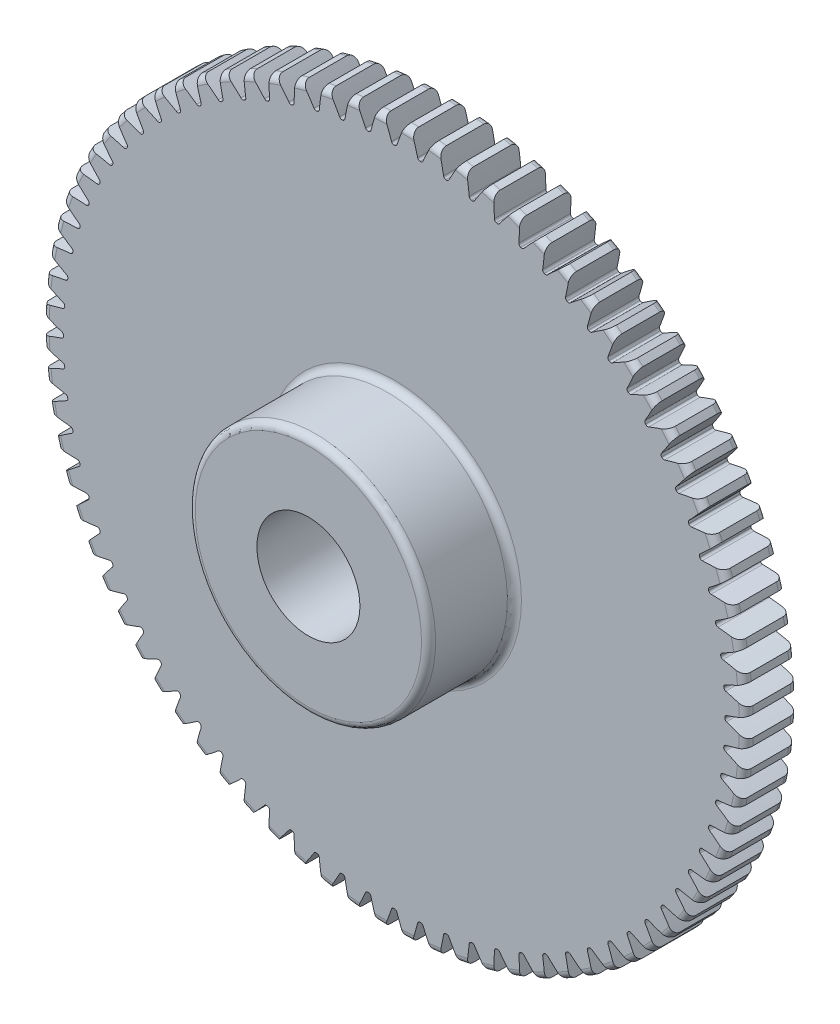
SolidWorks part; units mm, degrees
ref_plane "Front Plane" through (0, 0, 0) normal (0, 0, 1) x (1, 0, 0)
ref_plane "Top Plane" through (0, 0, 0) normal (0, 1, 0) x (1, 0, 0)
ref_plane "Right Plane" through (0, 0, 0) normal (1, 0, 0) x (0, 0, -1)
sketch "Sketch1" plane through (0, 0, 0) normal (0, 0, 1) x (1, 0, 0)
  line L0 (-1016, 0) -> (1016, 0) construction
  circle A0 centre (0, 0) radius 20.5 construction
  circle A1 centre (0, 0) radius 20 construction
  circle A2 centre (0, 0) radius 19.25 construction
  circle A3 centre (0, 0) radius 7 construction
  circle A4 centre (0, 0) radius 3 construction
  dimension "D2" = 0.5
  dimension "D3" = 1.25
  dimension "D1" = 1.25
sketch "Sketch2" plane through (0, 0, 0) normal (1, 0, 0) x (0, 0, -1)
  line L0 (0, 0) -> (-3, 0) construction
  line L1 (-3, 0) -> (-8, 0) construction
  dimension "Overall Width" = 8
  dimension "Face Width" = 3
sketch "Sketch4" plane through (0, 0, 0) normal (1, 0, 0) x (0, 0, -1)
  line L0 (-8, 3) -> (-8, 7)
  line L1 (-8, 7) -> (-3, 7)
  line L2 (-3, 7) -> (-3, 20.5)
  line L3 (-3, 20.5) -> (0, 20.5)
  line L4 (0, 20.5) -> (0, 3)
  line L5 (-3, 7) -> (-3, 0) construction
  line L6 (0, 20.5) -> (0, -20.5) construction
  line L7 (-3, 7) -> (0, 7) construction
  line L12 (-8, 3) -> (0, 3)
revolve "Revolve1" add sketch "Sketch4" angle 360 about L1
fillet "Fillet2" radius 0.41 4 edges at (0, 7, 8) (0, 7, 3) (0, 20.5, 3) (0, 20.5, 0)
sketch "Sketch7" plane through (0, 0, 3) normal (0, 0, 1) x (1, 0, 0)
  line L0 (0, 0) -> (0, 20.5) construction
  line L1 (0.3927, 19.9961) -> (0.5841, 20.4917) construction
  line L3 (0.8048, 20.4842) -> (0.7852, 19.9846) construction
  line L4 (0.7852, 19.9846) -> (0.7558, 19.2352) construction
  line L5 (0, 0) -> (0.7558, 19.2352) construction
  line L6 (0.3927, 19.9961) -> (0, 0) construction
  line L7 (0.3927, 19.9961) -> (0.4025, 20.496) construction
  line L8 (0.3927, 19.9961) -> (0, 0) construction
  circle A0 centre (0, 0) radius 20.5 construction
  arc A1 (-0.0142, 19.25) -> (0.0142, 19.25) centre (0, 0) cw
  circle A2 centre (0, 0) radius 19.25 construction
  arc A3 (-0.3927, 19.9961) -> (0.3927, 19.9961) centre (0, 0) cw construction
  circle A4 centre (0, 0) radius 20 construction
  arc A5 (1.0179, 20.4747) -> (0.5917, 20.4915) centre (0, 0) ccw construction
  arc A6 (0.3927, 19.9961) -> (1.1774, 19.9653) centre (0, 0) cw construction
  arc A7 (-0.5917, 20.4915) -> (0.5917, 20.4915) centre (0, 0) cw
  arc A8 (0.156, 19.3508) -> (0.5917, 20.4915) centre (19.0486, 12.7881) cw
  arc A9 (-0.156, 19.3508) -> (-0.5917, 20.4915) centre (-19.0486, 12.7881) ccw
  arc A10 (-0.0142, 19.25) -> (-0.156, 19.3508) centre (-0.0143, 19.4) cw
  arc A11 (0.0142, 19.25) -> (0.156, 19.3508) centre (0.0143, 19.4) ccw
  point P26 (-0.1212, 19.2496)
  point P29 (0.1212, 19.2496)
  dimension "D4" = 0.15
  dimension "D5" = 20
  dimension "D3" = 20
  dimension "D1" = 1.5708
  dimension "D2" = 0.7854
extrude "Cut-Extrude2" cut sketch "Sketch7" against normal through all
pattern_circular "CirPattern1" count 80 over 360 about axis through (0, 0, 8) along (0, 0, -1) of "Cut-Extrude2"
equation "\"D1@Sketch1\"=2.5*(\"Pitch Dia.@Sketch1\"/\"Number of Teeth@Sketch1\")"
equation "\"D1@CirPattern1\"=\"Number of Teeth@Sketch1\""
equation "\"D1@Fillet2\"=\"OD@Sketch1\"*.01"
equation "\"D1@Sketch7\"=3.14159*(\"Pitch Dia.@Sketch1\"/\"Number of Teeth@Sketch1\")"
equation "\"D2@Sketch7\"=\"D1@Sketch7\"/2"
equation "\"D4@Sketch7\"=\"D1@Sketch7\"*.0955"
equation "\"D5@Sketch7\"=\"Pitch Dia.@Sketch1\"/2"
